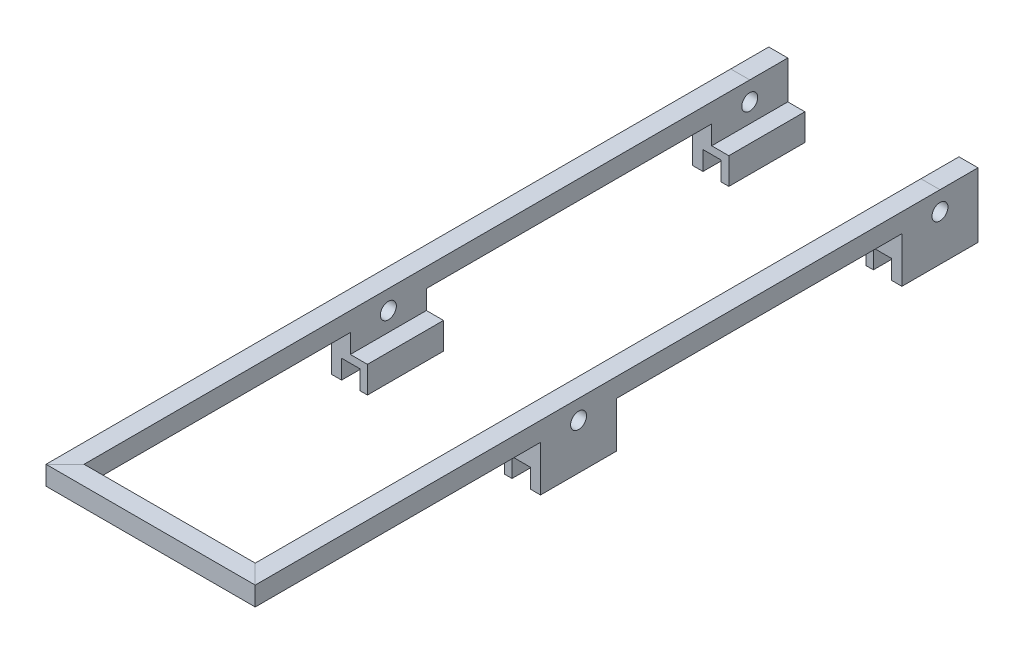
SolidWorks part; units mm, degrees
ref_plane "Front Plane" through (0, 0, 0) normal (0, 0, 1) x (1, 0, 0)
ref_plane "Top Plane" through (0, 0, 0) normal (0, 1, 0) x (1, 0, 0)
ref_plane "Right Plane" through (0, 0, 0) normal (1, 0, 0) x (0, 0, -1)
sketch "rail_path" plane through (0, 0, 0) normal (0, 1, 0) x (1, 0, 0)
  line L0 (28.575, 111.125) -> (28.575, 123.825)
  line L1 (-28.575, -111.125) -> (28.575, -111.125)
  line L2 (-28.575, -111.125) -> (-28.575, 111.125)
  line L3 (-28.575, 111.125) -> (28.575, 111.125) construction
  line L4 (28.575, -111.125) -> (28.575, 111.125)
  line L5 (-28.575, -111.125) -> (28.575, 111.125) construction
  line L6 (-28.575, 111.125) -> (28.575, -111.125) construction
  line L7 (-28.575, 111.125) -> (-28.575, 123.825)
  point P0 (0, 0)
  dimension "D1" = 222.25
  dimension "D2" = 57.15
  dimension "D3" = 12.7
  dimension "D4" = 12.7
sketch "rail_profile" plane through (0, 0, 0) normal (0, 0, 1) x (1, 0, 0)
  line L0 (-28.575, 0) -> (28.575, 0) construction
  line L1 (28.575, 0) -> (34.925, 0)
  line L2 (28.575, 0) -> (28.575, 6.35)
  line L3 (28.575, 6.35) -> (34.925, 6.35)
  line L4 (34.925, 0) -> (34.925, 6.35)
  line L5 (-28.575, 0) -> (28.575, 0) construction
  dimension "D1" = 6.35
  dimension "D2" = 6.35
sweep "Sweep1" add profiles "rail_profile" path "rail_path"
sketch "clip_profile" plane through (0, 0, 0) normal (0, 0, 1) x (1, 0, 0)
  line L2 (34.925, 0) -> (28.575, 0)
  line L4 (28.575, 0) -> (-28.575, 0)
  line L12 (-28.575, 6.35) -> (28.575, 6.35)
  line L16 (28.575, 0) -> (28.575, -6.35)
  line L18 (34.925, 0) -> (34.925, -6.35)
  line L19 (28.575, -6.35) -> (34.925, -6.35) construction
  line L30 (34.925, -6.35) -> (28.575, -6.35) construction
  line L31 (28.575, -6.35) -> (22.86, -6.35)
  line L33 (34.925, -6.35) -> (34.925, -15.24)
  line L34 (34.925, -15.24) -> (31.496, -15.24)
  line L35 (22.86, -6.35) -> (22.86, -15.24)
  line L37 (25.4, -15.24) -> (25.4, -8.89)
  line L38 (25.4, -8.89) -> (31.496, -8.89)
  line L39 (31.496, -15.24) -> (31.496, -8.89)
  line L40 (31.496, -15.24) -> (25.4, -15.24) construction
  line L41 (25.4, -15.24) -> (22.86, -15.24)
  line L42 (34.925, 6.35) -> (34.925, 0)
  line L43 (34.925, 0) -> (28.575, 0)
  line L45 (-28.575, 0) -> (-34.925, 0)
  line L46 (-34.925, 0) -> (-34.925, 6.35)
  line L47 (-34.925, 6.35) -> (-28.575, 6.35)
  line L49 (28.575, 6.35) -> (34.925, 6.35)
  dimension "D1" = 6.35
  dimension "D2" = 6.096
  dimension "D4" = 6.35
  dimension "D5" = 8.89
  dimension "D6" = 6.35
  dimension "D7" = 3.175
  dimension "D3" = 2.54
ref_plane "FrontClipPlane" through (0, 0, -111.125) normal (0, 0, -1) x (-1, 0, 0)
ref_plane "BackClipPlane" through (0, 0, 9.525) normal (0, 0, -1) x (-1, 0, 0)
sketch "BackClipProfile" plane through (0, 0, 9.525) normal (0, 0, -1) x (-1, 0, 0)
  line L0 (-34.925, 0) -> (-28.575, 0) construction
  line L1 (-28.575, -6.35) -> (-22.86, -6.35) construction
  line L2 (-22.86, -6.35) -> (-22.86, -15.24) construction
  line L3 (-25.4, -15.24) -> (-22.86, -15.24) construction
  line L4 (-25.4, -15.24) -> (-25.4, -8.89) construction
  line L5 (-25.4, -8.89) -> (-31.496, -8.89) construction
  line L6 (-31.496, -15.24) -> (-31.496, -8.89) construction
  line L7 (-34.925, -15.24) -> (-31.496, -15.24) construction
  line L8 (-34.925, -6.35) -> (-34.925, -15.24) construction
  line L10 (-28.575, 0) -> (-28.575, -6.35) construction
  line L11 (-34.925, 0) -> (-34.925, -6.35) construction
  line L12 (-34.925, 0) -> (-28.575, 0)
  line L13 (-28.575, -6.35) -> (-22.86, -6.35)
  line L14 (-22.86, -6.35) -> (-22.86, -15.24)
  line L15 (-25.4, -15.24) -> (-22.86, -15.24)
  line L16 (-25.4, -15.24) -> (-25.4, -8.89)
  line L17 (-25.4, -8.89) -> (-31.496, -8.89)
  line L18 (-31.496, -15.24) -> (-31.496, -8.89)
  line L19 (-34.925, -15.24) -> (-31.496, -15.24)
  line L20 (-34.925, -6.35) -> (-34.925, -15.24)
  line L22 (-28.575, 0) -> (-28.575, -6.35)
  line L23 (-34.925, 0) -> (-34.925, -6.35)
sketch "FrontClipProfile" plane through (0, 0, -111.125) normal (0, 0, -1) x (-1, 0, 0)
  line L0 (-34.925, -15.24) -> (-31.496, -15.24) construction
  line L1 (-31.496, -15.24) -> (-31.496, -8.89) construction
  line L2 (-25.4, -8.89) -> (-31.496, -8.89) construction
  line L3 (-25.4, -15.24) -> (-25.4, -8.89) construction
  line L4 (-25.4, -15.24) -> (-22.86, -15.24) construction
  line L5 (-22.86, -6.35) -> (-22.86, -15.24) construction
  line L6 (-28.575, -6.35) -> (-22.86, -6.35) construction
  line L8 (-34.925, -6.35) -> (-34.925, -15.24) construction
  line L9 (-28.575, 0) -> (-28.575, -6.35) construction
  line L10 (-34.925, 0) -> (-34.925, -6.35) construction
  line L11 (-34.925, 0) -> (-28.575, 0) construction
  line L12 (-34.925, -15.24) -> (-31.496, -15.24)
  line L13 (-31.496, -15.24) -> (-31.496, -8.89)
  line L14 (-25.4, -8.89) -> (-31.496, -8.89)
  line L15 (-25.4, -15.24) -> (-25.4, -8.89)
  line L16 (-25.4, -15.24) -> (-22.86, -15.24)
  line L17 (-22.86, -6.35) -> (-22.86, -15.24)
  line L18 (-28.575, -6.35) -> (-22.86, -6.35)
  line L20 (-34.925, -6.35) -> (-34.925, -15.24)
  line L21 (-28.575, 0) -> (-28.575, -6.35)
  line L22 (-34.925, 0) -> (-34.925, -6.35)
  line L23 (-34.925, 0) -> (-28.575, 0)
extrude "BackClip" add sketch "BackClipProfile" along normal mid plane 25.4
mirror "BackClipMirror" about plane through (0, 0, 0) normal (1, 0, 0) of "BackClip"
extrude "FrontClip" add sketch "FrontClipProfile" along normal mid plane 25.4
mirror "FrontClipMirror" about plane through (0, 0, 0) normal (1, 0, 0) of "FrontClip"
sketch "Sketch8" plane through (28.575, 0, 0) normal (-1, 0, 0) x (0, 0, 1)
  line L0 (-123.825, 6.35) -> (-123.825, -6.35) construction
  line L1 (-123.825, -6.35) -> (-98.425, -6.35) construction
  line L2 (-98.425, -6.35) -> (-98.425, 0) construction
  line L9 (111.125, 6.35) -> (-111.125, 6.35) construction
  line L12 (-111.125, 6.35) -> (-123.825, 6.35) construction
  line L13 (-98.425, -6.35) -> (-98.425, 0) construction
  line L14 (-123.825, -6.35) -> (-98.425, -6.35) construction
  line L15 (-111.125, 6.35) -> (-123.825, 6.35) construction
  line L16 (-123.825, 6.35) -> (-123.825, -6.35) construction
  line L17 (111.125, 6.35) -> (-111.125, 6.35) construction
  line L18 (-123.825, 6.35) -> (-98.425, -6.35) construction
  line L19 (22.225, -6.35) -> (22.225, 0) construction
  line L20 (-3.175, -6.35) -> (22.225, -6.35) construction
  line L21 (-3.175, -6.35) -> (-3.175, 0) construction
  line L22 (22.225, -6.35) -> (22.225, 0) construction
  line L23 (-3.175, -6.35) -> (22.225, -6.35) construction
  line L24 (-3.175, -6.35) -> (-3.175, 0) construction
  line L25 (-3.175, -6.35) -> (22.225, 6.35) construction
  circle A0 centre (-111.125, 0) radius 2.667
  circle A1 centre (9.525, 0) radius 2.667
  dimension "D1" = 5.334
  dimension "D2" = 5.334
extrude "Cut-Extrude1" cut sketch "Sketch8" against normal through all both and the other way through all
equation "\"rail_horizontal_clearance\"= 0.25 / 2"
